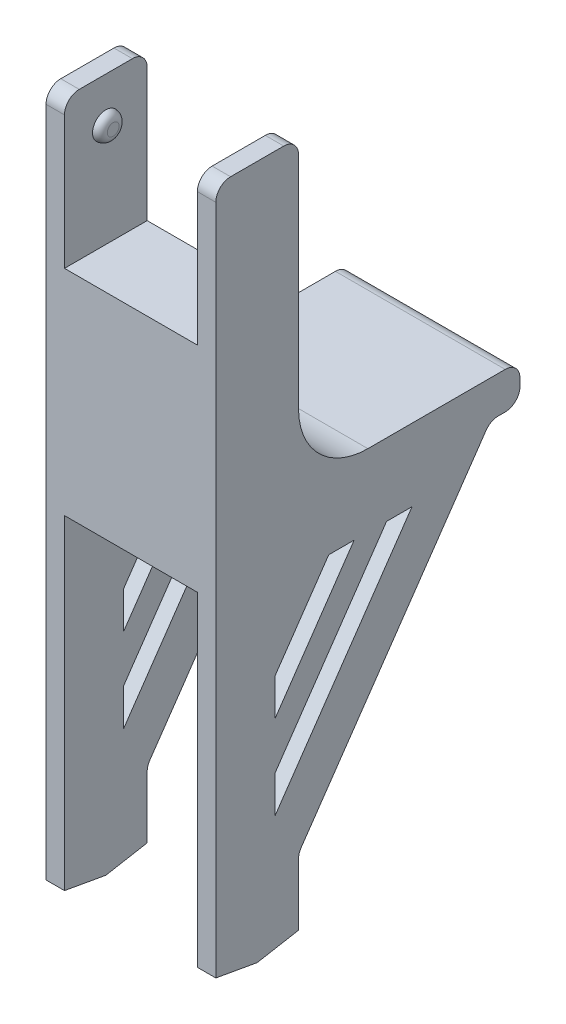
SolidWorks part; units mm, degrees
ref_plane "Front Plane" through (0, 0, 0) normal (0, 0, 1) x (1, 0, 0)
ref_plane "Top Plane" through (0, 0, 0) normal (0, 1, 0) x (1, 0, 0)
ref_plane "Right Plane" through (0, 0, 0) normal (1, 0, 0) x (0, 0, -1)
sketch "Szkic1" plane through (0, 0, 0) normal (1, 0, 0) x (0, 0, -1)
  line L2 (0, 0) -> (-10.3, 0)
  line L5 (-15, 4.7) -> (-15, 20.6)
  line L6 (-15, 20.6) -> (-20.6, 20.6)
  line L7 (-20.6, 20.6) -> (-20.6, -21.4)
  line L8 (0, 0) -> (0, -2.5)
  line L9 (0, -2.5) -> (-2, -2.5)
  line L10 (-2, -2.5) -> (-15, -21.4)
  line L11 (-15, -21.4) -> (-15, -25.9)
  line L13 (-20.6, -25.9) -> (-20.6, -21.4)
  line L20 (-20.6, -25.9) -> (-17.8, -26.4)
  line L21 (-17.8, -26.4) -> (-15, -25.9)
  arc A0 (-15, 4.7) -> (-10.3, 0) centre (-10.3, 4.7) ccw
  point P15 (-10.3, 4.7)
  dimension "D5" = 2.5
  dimension "D7" = 4.7
  dimension "D1" = 42
  dimension "D2" = 20.6
  dimension "D3" = 15.9
  dimension "D4" = 5.6
  dimension "D6" = 2
  dimension "D8" = 18.9
  dimension "D9" = 4.5
  dimension "D10" = 0.5
  dimension "D11" = 4.5
extrude "Dodanie-wyciągnięcie1" add sketch "Szkic1" along normal blind 11.5
ref_plane "Płaszczyzna dolna" through (0, 0, 20.6) normal (0, 0, 1) x (1, 0, 0)
sketch "Szkic2" plane through (0, 0, 20.6) normal (0, 0, 1) x (1, 0, 0)
  line L0 (5.75, 20.6) -> (5.75, -25.9) construction
  line L1 (11.5, 20.6) -> (0, 20.6) construction
  line L4 (10.25, 10.6) -> (1.25, 10.6)
  line L5 (10.25, 10.6) -> (10.25, 20.6)
  line L6 (10.25, 20.6) -> (1.25, 20.6)
  line L7 (1.25, 10.6) -> (1.25, 20.6)
  line L8 (10.25, 10.6) -> (1.25, 20.6) construction
  line L9 (10.25, 20.6) -> (1.25, 10.6) construction
  line L10 (10.25, -3.9) -> (1.25, -3.9)
  line L11 (10.25, -3.9) -> (10.25, -28.2703)
  line L12 (10.25, -28.2703) -> (1.25, -28.2703)
  line L13 (1.25, -3.9) -> (1.25, -28.2703)
  line L14 (10.25, -3.9) -> (1.25, -28.2703) construction
  line L15 (10.25, -28.2703) -> (1.25, -3.9) construction
  point P6 (5.75, 15.6)
  point P11 (5.75, -14.9)
  dimension "D1" = 9
  dimension "D2" = 10
  dimension "D3" = 9
  dimension "D4" = 11
extrude "Wytnij-wyciągnięcie1" cut sketch "Szkic2" against normal through all
ref_plane "Płaszczyzna boczna" through (11.5, 0, 0) normal (1, 0, 0) x (0, 0, -1)
sketch "Szkic3" plane through (11.5, 0, 0) normal (1, 0, 0) x (0, 0, -1)
  line L0 (-16.6, -12.7056) -> (-16.6, -10.1985)
  line L1 (-16.6, -10.1985) -> (-12.9555, -4.9)
  line L2 (-12.9555, -4.9) -> (-11.2311, -4.9)
  line L3 (-11.2311, -4.9) -> (-16.6, -12.7056)
  line L4 (-16.6, -15.8972) -> (-16.6, -18.4043)
  line L5 (-16.6, -18.4043) -> (-7.3113, -4.9)
  line L6 (-7.3113, -4.9) -> (-9.0358, -4.9)
  line L7 (-9.0358, -4.9) -> (-16.6, -15.8972)
  line L8 (-15, -21.4) -> (-2, -2.5) construction
  line L10 (-20.6, 6.325) -> (-20.6, -6.325) construction
  dimension "D1" = 4
  dimension "D2" = 21
extrude "Wytnij-wyciągnięcie2" cut sketch "Szkic3" against normal through all both and the other way through all
fillet "Zaokrąglenie2" radius 1 9 edges at (5.75, 0, 0) (5.75, -2.5, 0) (10.875, 20.6, 20.6) (10.875, 20.6, 15) (0.625, 20.6, 20.6) (0.625, 20.6, 15) (5.75, -2.5, 2) (0.625, -21.4, 15) (10.875, -21.4, 15)
ref_plane "Płaszczyzna4" through (10.25, 0, 0) normal (-1, 0, 0) x (0, 0, 1)
sketch "Szkic5" plane through (10.25, 0, 0) normal (-1, 0, 0) x (0, 0, 1)
  line L3 (17.8, 20.6) -> (17.8, 10.6) construction
  line L4 (16, 20.6) -> (19.6, 20.6) construction
  line L5 (15, 10.6) -> (20.6, 10.6) construction
  circle A0 centre (17.8, 17.6) radius 0.9
  dimension "D1" = 1.8
  dimension "D2" = 3
extrude "Dodanie-wyciągnięcie2" add sketch "Szkic5" along normal blind 0.5
fillet "Zaokrąglenie3" radius 0.5 1 edges at (9.75, 16.7, 17.8)
ref_plane "Płaszczyzna5" through (5.75, 0, 0) normal (1, 0, 0) x (0, 0, -1)
mirror "Lustro2" about plane through (5.75, 0, 0) normal (1, 0, 0) of bodies 113 115
sketch "Szkic7" plane through (1.25, 0, 0) normal (1, 0, 0) x (0, 0, -1)
  line L0 (0, -1.25) -> (-2.8277, -1.25) construction
  line L1 (0, -1.5) -> (0, -1) construction
  circle A0 centre (-1.1, -1.25) radius 0.5
  dimension "D1" = 1
  dimension "D2" = 1.1
extrude "Dodanie-wyciągnięcie3" add sketch "Szkic7" along normal up to surface (9 mm away) up to face at (10.25, -11.0254, 12.3868)
